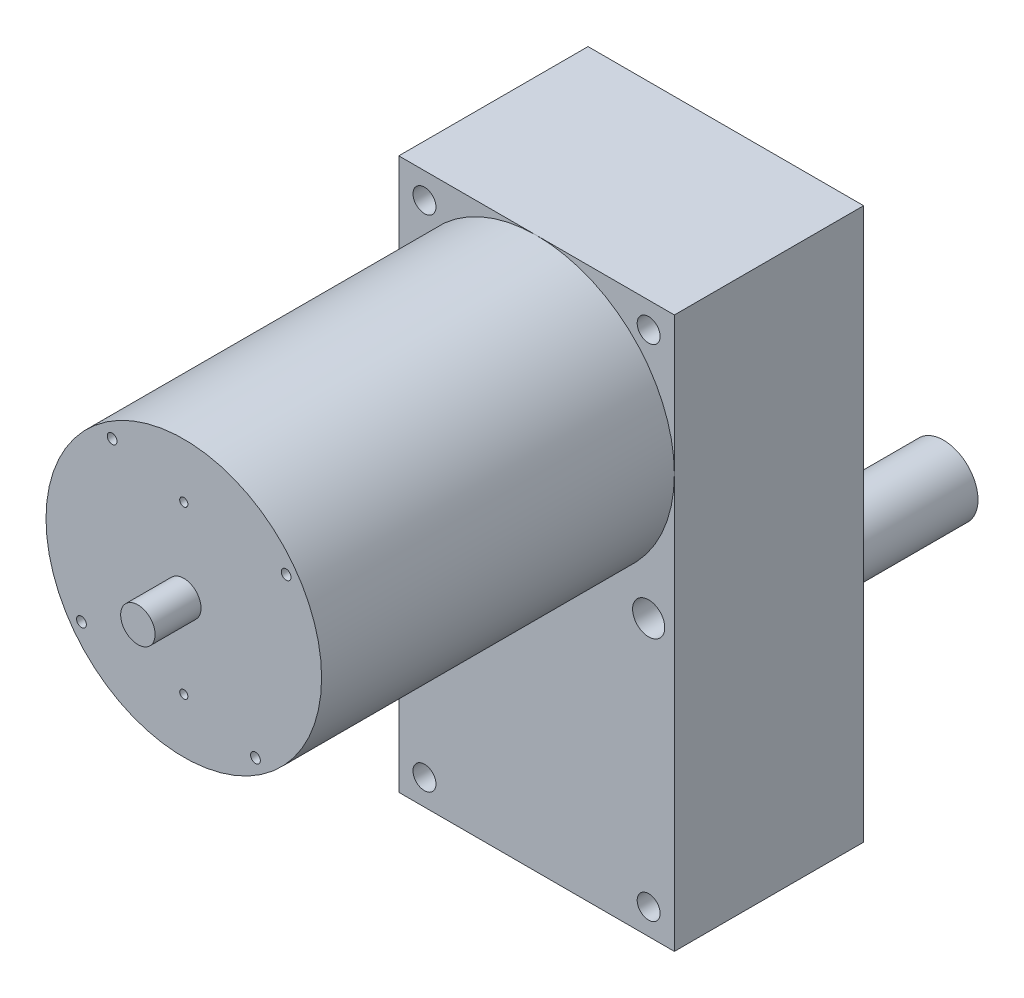
SolidWorks part; units mm, degrees
ref_plane "前视基准面" through (0, 0, 0) normal (0, 0, 1) x (1, 0, 0)
ref_plane "上视基准面" through (0, 0, 0) normal (0, 1, 0) x (1, 0, 0)
ref_plane "右视基准面" through (0, 0, 0) normal (1, 0, 0) x (0, 0, -1)
sketch "Sketch1" plane through (0, 0, 0) normal (0, 0, 1) x (1, 0, 0)
  line L0 (0, 76.2) -> (0, -14.7176) construction
  line L1 (38.1, -76.2) -> (-38.1, -76.2)
  line L2 (38.1, -76.2) -> (38.1, 76.2)
  line L3 (38.1, 76.2) -> (-38.1, 76.2)
  line L4 (-38.1, -76.2) -> (-38.1, 76.2)
  line L5 (38.1, -76.2) -> (-38.1, 76.2) construction
  line L6 (38.1, 76.2) -> (-38.1, -76.2) construction
  line L7 (38.1, 0) -> (-38.1, 0) construction
  circle A0 centre (0, 38.608) radius 23.495
  circle A1 centre (0, -38.608) radius 23.495
  circle A2 centre (-30.988, 0) radius 4.445
  circle A3 centre (30.9942, -69.088) radius 3.175
  circle A4 centre (-30.9942, -69.088) radius 3.175
  circle A5 centre (-30.988, 69.088) radius 3.175
  circle A6 centre (30.988, 0) radius 4.445
  circle A7 centre (30.988, 69.088) radius 3.175
  circle A8 centre (0, -38.608) radius 9.525
  circle A9 centre (0, -38.608) radius 3.9688
  point P0 (0, 0)
  dimension "D3" = 46.99
  dimension "D6" = 46.99
  dimension "D7" = 6.35
  dimension "D8" = 6.35
  dimension "D12" = 8.89
  dimension "D14" = 19.05
  dimension "D15" = 7.9375
  dimension "D1" = 152.4
  dimension "D2" = 76.2
  dimension "D4" = 38.608
  dimension "D5" = 38.608
  dimension "D9" = 30.988
  dimension "D10" = 69.088
  dimension "D11" = 69.088
  dimension "D13" = 30.988
extrude "Boss-Extrude1" add sketch "Sketch1" along normal blind 52.324 contours L4 L1 L2 L3 A6 A5 A4 A0 A1 A2 A3 A7 | A0 | A1 A8 | A9 | A8 A9 region at (0, 0, 0) region at (0, 38.608, 0) region at (-22.8305, -38.608, 0) region at (-9.2556, -38.608, 0) region at (0, -38.608, 0)
extrude "Boss-Extrude2" add sketch "Sketch1<3>" against normal blind 4.826 contours A0 | A1 A8 region at (0, 38.608, 0) region at (-22.8305, -38.608, 0)
sketch "Sketch1<3>" plane through (0, 0, 0) normal (0, 0, 1) x (1, 0, 0) same geometry as "Sketch1"
extrude "Boss-Extrude3" add sketch "Sketch1<5>" against normal blind 60.198 contours A8 A9 region at (-9.2556, -38.608, 0)
sketch "Sketch1<5>" plane through (0, 0, 0) normal (0, 0, 1) x (1, 0, 0) same geometry as "Sketch1"
sketch "Sketch2" plane through (0, 0, -60.198) normal (0, 0, -1) x (-1, 0, 0)
  line L0 (3.9688, -38.608) -> (9.525, -38.608) construction
  line L1 (8.9803, -35.433) -> (4.4279, -35.433)
  line L2 (4.4279, -35.433) -> (4.4279, -41.783)
  line L3 (8.9803, -41.783) -> (4.4279, -41.783)
  circle A0 centre (0, -38.608) radius 3.9688 construction
  circle A1 centre (0, -38.608) radius 9.525 construction
  arc A4 (8.9803, -35.433) -> (8.9803, -41.783) centre (0, -38.608) cw
  dimension "D1" = 3.175
extrude "Cut-Extrude1" cut sketch "Sketch2" against normal blind 26.924
sketch "Sketch4" plane through (0, 0, 52.324) normal (0, 0, 1) x (1, 0, 0)
  line L0 (38.1, 76.2) -> (-38.1, 76.2) construction
  circle A0 centre (0, 38.1) radius 38.1
  dimension "D2" = 76.2
  dimension "D1" = 38.1
extrude "Boss-Extrude4" add sketch "Sketch4" along normal blind 97.536
sketch "Sketch5" plane through (0, 0, 149.86) normal (0, 0, 1) x (1, 0, 0)
  circle A0 centre (0, 38.1) radius 4.7625
  dimension "D1" = 9.525
extrude "Boss-Extrude5" add sketch "Sketch5" along normal blind 12.7
hole_wizard "#4-40 Tapped Hole1" positions "Sketch7" profile "Sketch6" tap size "#4-40" standard "Ansi Inch"
sketch "Sketch7" plane through (0, 0, 149.86) normal (0, 0, 1) x (1, 0, 0)
  circle A0 centre (0, 38.1) radius 23 construction
  point P0 (0, 61.1)
  point P1 (0, 15.1)
  dimension "D1" = 46
sketch "Sketch6" plane through (0, 61.1, 149.86) normal (1, 0, 0) x (0, -1, 0)
  line L0 (0, 0) -> (0, 8.2792)
  line L1 (0, 8.2792) -> (1.1303, 7.6)
  line L2 (1.1303, 7.6) -> (1.1303, 0)
  line L5 (1.1303, 0) -> (0, 0)
  line L10 (0, 8.2792) -> (-1.1303, 7.6) construction
  line L11 (0, -6.35) -> (0, 107.95) construction
  dimension "Tap Drill Dia." = 2.2606
  dimension "Tap Drill Depth" = 7.6
  dimension "Drill Angle" = 118
hole_wizard "#6-32 Tapped Hole1" positions "Sketch9" profile "Sketch8" tap size "#6-32" standard "Ansi Inch"
sketch "Sketch9" plane through (0, 0, 149.86) normal (0, 0, 1) x (1, 0, 0)
  line L0 (-19.8136, 66.3968) -> (19.8136, 9.8032)
  line L2 (28.2968, 57.9136) -> (-28.2968, 18.2864)
  line L4 (0, 0) -> (0, 38.1) construction
  circle A0 centre (0, 38.1) radius 34.544
  point P0 (28.2968, 57.9136)
  point P1 (19.8136, 9.8032)
  point P3 (-28.2968, 18.2864)
  point P5 (-19.8136, 66.3968)
  dimension "D2" = 69.088
  dimension "D1" = 35
sketch "Sketch8" plane through (28.2968, 57.9136, 149.86) normal (1, 0, 0) x (0, -1, 0)
  line L0 (0, 0) -> (0, 10.2027)
  line L1 (0, 10.2027) -> (1.3525, 9.39)
  line L2 (1.3525, 9.39) -> (1.3525, 0)
  line L5 (1.3525, 0) -> (0, 0)
  line L10 (0, 10.2027) -> (-1.3526, 9.39) construction
  line L11 (0, -6.35) -> (0, 107.95) construction
  dimension "Tap Drill Dia." = 2.7051
  dimension "Tap Drill Depth" = 9.39
  dimension "Drill Angle" = 118
